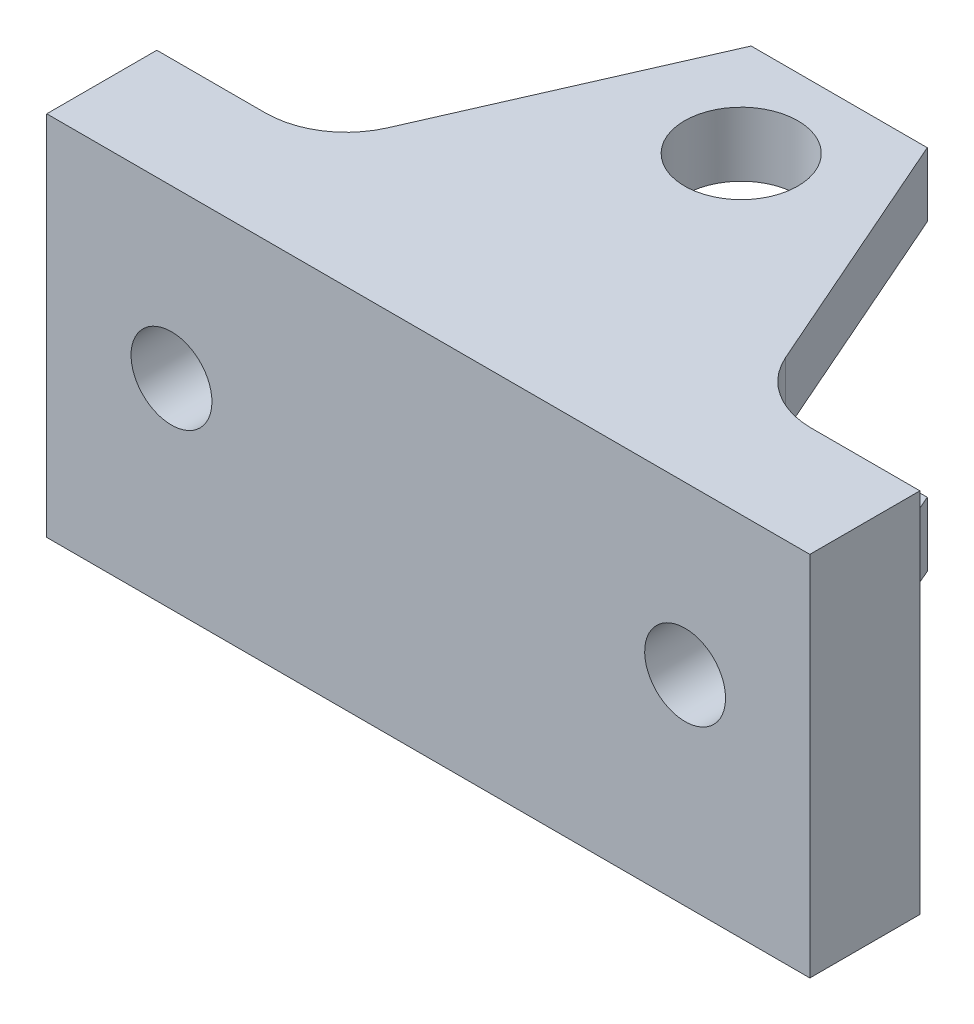
SolidWorks part; units mm, degrees
material "Custom Plastic"
ref_plane "X-Y Datum" through (0, 0, 0) normal (0, 0, 1) x (1, 0, 0)
ref_plane "X-Z Datum" through (0, 0, 0) normal (0, 1, 0) x (1, 0, 0)
ref_plane "Y-Z Datum" through (0, 0, 0) normal (1, 0, 0) x (0, 0, -1)
sketch "Sketch1" plane through (0, 0, 0) normal (1, 0, 0) x (0, 0, -1)
  line L0 (0, 8.7126) -> (0, 40.4626)
  line L1 (0, 40.4626) -> (39.7797, 40.4626)
  line L2 (39.7797, 40.4626) -> (39.7797, 34.9127)
  line L3 (39.7797, 34.9127) -> (9.525, 34.9127)
  line L4 (9.525, 34.9127) -> (9.525, 14.2625)
  line L5 (9.525, 14.2625) -> (39.7797, 14.2625)
  line L6 (39.7797, 14.2625) -> (39.7797, 8.7126)
  line L7 (39.7797, 8.7126) -> (0, 8.7126)
  line L8 (29.6197, 40.4626) -> (29.6197, 8.7126) construction
  line L9 (0, 26.0299) -> (9.525, 26.0299) construction
  line L10 (0, 22.0299) -> (0, 30.0299) construction
  circle A0 centre (29.6197, 24.5876) radius 10.3251 construction
  dimension "D5" = 20.6502
  dimension "D1" = 20.6502
  dimension "D2" = 31.75
  dimension "D3" = 10.16
  dimension "D4" = 9.525
extrude "Boss-Extrude1" add sketch "Sketch1" along normal blind 76.2
sketch "Sketch2" plane through (0, 0, -9.525) normal (0, 0, -1) x (-1, 0, 0)
  line L0 (-38.1, 34.9127) -> (-38.1, 14.2625) construction
  line L1 (-76.2, 34.9127) -> (0, 34.9127) construction
  line L2 (-76.2, 14.2625) -> (0, 14.2625) construction
  line L3 (-60.325, 26.0299) -> (-15.875, 26.0299) construction
  circle A0 centre (-60.325, 26.0299) radius 3.4
  circle A1 centre (-15.875, 26.0299) radius 3.4
  point P8 (-38.1, 26.0299)
  dimension "D2" = 6.8
  dimension "D1" = 44.45
extrude "Cut-Extrude1" cut sketch "Sketch2" against normal up to surface (9.525 mm away) up to face at (38.1, 24.5876, 0)
sketch "Sketch3" plane through (0, 40.4626, 0) normal (0, 1, 0) x (1, 0, 0)
  line L0 (76.2, 39.7797) -> (0, 39.7797) construction
  line L1 (30.48, 35.56) -> (19.05, 9.525)
  line L2 (45.72, 35.56) -> (57.15, 9.525)
  line L3 (30.48, 35.56) -> (45.72, 35.56)
  line L4 (0, 39.7797) -> (0, 9.525)
  line L5 (0, 0) -> (0, 39.7797) construction
  line L6 (0, 9.525) -> (19.05, 9.525)
  line L7 (0, 39.7797) -> (76.2, 39.7797)
  line L8 (76.2, 39.7797) -> (76.2, 9.525)
  line L9 (76.2, 39.7797) -> (76.2, 0) construction
  line L10 (76.2, 9.525) -> (57.15, 9.525)
  line L12 (76.2, 0) -> (0, 0) construction
  circle A0 centre (38.1, 27.0797) radius 3.2639
  point P4 (38.1, 39.7797)
  dimension "D1" = 6.5278
  dimension "D2" = 12.7
  dimension "D3" = 15.24
  dimension "D4" = 35.56
  dimension "D5" = 19.05
extrude "Cut-Extrude2" cut sketch "Sketch3" against normal up to surface (31.75 mm away) up to face at (38.1, 8.7126, -19.8899)
sketch "Sketch4" plane through (0, 0, -9.525) normal (0, 0, -1) x (-1, 0, 0)
  line L0 (0, 40.4626) -> (-19.05, 40.4626) construction
  line L1 (0, 8.7126) -> (-5.08, 8.7126)
  line L2 (0, 8.7126) -> (0, 40.4626)
  line L3 (0, 40.4626) -> (-5.08, 40.4626)
  line L4 (-5.08, 8.7126) -> (-5.08, 40.4626)
  line L5 (-57.15, 40.4626) -> (-76.2, 40.4626) construction
  line L6 (-76.2, 8.7126) -> (-71.12, 8.7126)
  line L7 (-76.2, 8.7126) -> (-76.2, 40.4626)
  line L8 (-76.2, 40.4626) -> (-71.12, 40.4626)
  line L9 (-71.12, 8.7126) -> (-71.12, 40.4626)
  dimension "D1" = 5.08
extrude "Cut-Extrude3" cut sketch "Sketch4" against normal up to surface (9.525 mm away) up to face at (60.325, 29.4299, 0)
fillet "Fillet1" radius 6.985 4 edges at (57.15, 37.6877, -9.525) (57.15, 11.4876, -9.525) (19.05, 37.6877, -9.525) (19.05, 11.4876, -9.525)
sketch "Sketch5" plane through (0, 0, -9.525) normal (0, 0, -1) x (-1, 0, 0)
  circle A0 centre (-60.325, 26.0299) radius 3.5
  circle A1 centre (-15.875, 26.0299) radius 3.5
  dimension "D1" = 7
extrude "Cut-Extrude4" cut sketch "Sketch5" against normal through all both and the other way through all
ref_plane "Plane1" through (0, 46.5586, 0) normal (0, -1, 0) x (-1, 0, 0)
sketch "Sketch6" plane through (0, 46.5586, 0) normal (0, -1, 0) x (-1, 0, 0)
  line L0 (-76.2, -3.81) -> (0, -3.81)
  line L1 (-76.2, -3.81) -> (-76.2, 39.37)
  line L2 (0, -3.81) -> (0, 39.37)
  line L3 (-76.2, 39.37) -> (0, 39.37)
  line L4 (-38.1, 39.37) -> (-38.1, -3.81) construction
  line L5 (-38.1, 35.56) -> (-38.1, 0) construction
  line L6 (-45.72, 35.56) -> (-30.48, 35.56) construction
  line L7 (-5.08, 4.7625) -> (-71.12, 4.7625) construction
  line L8 (-5.08, 0) -> (-5.08, 9.525) construction
  line L9 (-71.12, 0) -> (-71.12, 9.525) construction
  line L10 (-71.12, 0) -> (-5.08, 0) construction
  line L12 (-76.2, 17.78) -> (0, 17.78)
  point P12 (-38.1, 4.7625)
  point P13 (-38.1, 17.78)
  point P22 (-38.1, 17.78)
  dimension "D1" = 76.2
  dimension "1.7" = 43.18
sketch "Sketch7" plane through (0, 40.4626, 0) normal (0, 1, 0) x (1, 0, 0)
  line L0 (0, 17.78) -> (76.2, 17.78)
  line L1 (38.1, 39.37) -> (38.1, -3.81)
  line L4 (0, -3.81) -> (76.2, -3.81)
  line L5 (0, 39.37) -> (0, -3.81)
  line L6 (76.2, 39.37) -> (0, 39.37)
  line L7 (76.2, -3.81) -> (76.2, 39.37)
  line L8 (0, -3.81) -> (76.2, -3.81)
  line L9 (0, 39.37) -> (0, -3.81)
  line L10 (76.2, 39.37) -> (0, 39.37)
  line L11 (76.2, -3.81) -> (76.2, 39.37)
  point P10 (38.1, 17.78)
  dimension "D1" = 0
sketch "Sketch8" plane through (0, 8.7126, 0) normal (0, -1, 0) x (1, 0, 0)
  line L4 (76.2, 3.81) -> (0, 3.81)
  line L5 (0, 3.81) -> (0, -39.37)
  line L6 (0, -39.37) -> (76.2, -39.37)
  line L7 (76.2, -39.37) -> (76.2, 3.81)
  line L8 (76.2, 3.81) -> (0, 3.81)
  line L9 (0, 3.81) -> (0, -39.37)
  line L10 (0, -39.37) -> (76.2, -39.37)
  line L11 (76.2, -39.37) -> (76.2, 3.81)
  point P0 (38.1, -17.78)
  dimension "D1" = 0
sketch "Sketch9" plane through (0, 8.7126, 0) normal (0, -1, 0) x (1, 0, 0)
  circle A0 centre (38.1, -27.0797) radius 4.9022
  circle A1 centre (38.1, -27.0797) radius 3.2639 construction
  dimension "D1" = 9.8044
extrude "Cut-Extrude5" cut sketch "Sketch9" against normal through all
